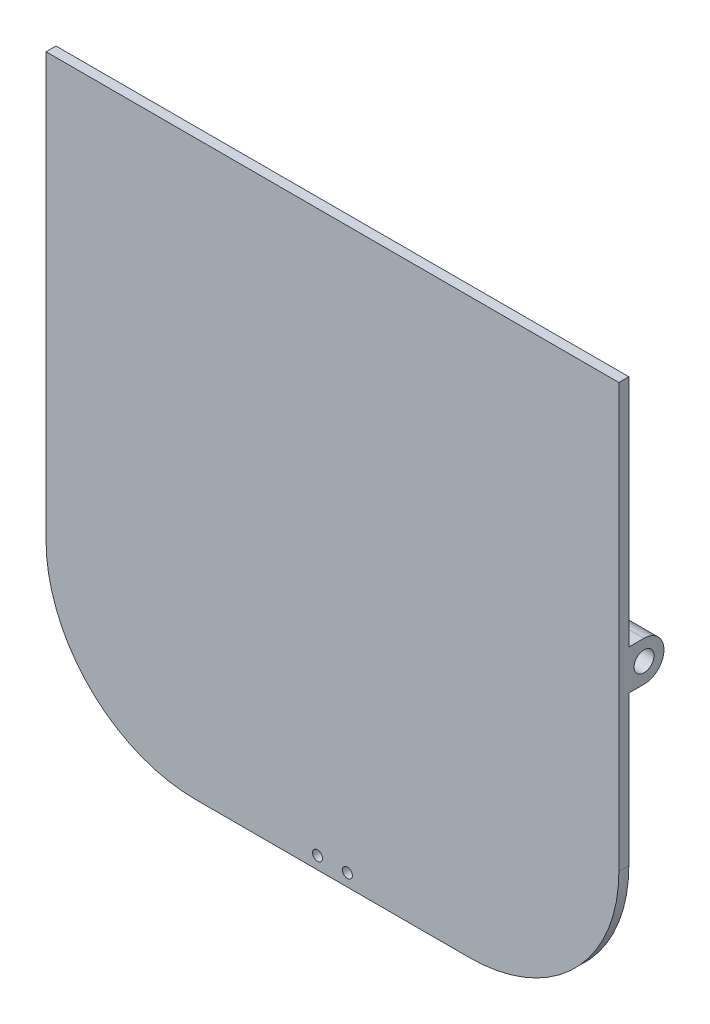
SolidWorks part; units mm, degrees
ref_plane "Płaszczyzna przednia" through (0, 0, 0) normal (0, 0, 1) x (1, 0, 0)
ref_plane "Płaszczyzna górna" through (0, 0, 0) normal (0, 1, 0) x (1, 0, 0)
ref_plane "Płaszczyzna prawa" through (0, 0, 0) normal (1, 0, 0) x (0, 0, -1)
sketch "Szkic1" plane through (0, 0, 0) normal (0, 0, 1) x (1, 0, 0)
  line L0 (0, -57.5) -> (115, -57.5) construction
  line L1 (0, 0) -> (115, 0)
  line L2 (0, 0) -> (0, -115)
  line L3 (0, -115) -> (115, -115)
  line L4 (115, 0) -> (115, -115)
  dimension "D1" = 115
  dimension "D2" = 115
extrude "Dodanie-wyciągnięcie1" add sketch "Szkic1" along normal blind 2
sketch "Szkic3" plane through (115, 0, 0) normal (1, 0, 0) x (0, 0, -1)
  line L0 (0, -115) -> (0, 0) construction
  line L1 (0, -47) -> (3.0506, -47)
  line L2 (0, -47) -> (0, -55)
  line L3 (0, -55) -> (3.0506, -55)
  line L6 (-2, -115) -> (0, -115) construction
  arc A0 (3.0506, -55) -> (3.0506, -47) centre (3.0506, -51) ccw
  dimension "D1" = 8
  dimension "D2" = 60
extrude "Dodanie-wyciągnięcie2" add sketch "Szkic3" against normal up to surface (115 mm away) up to face at (0, -57.5, 1)
sketch "Szkic5" plane through (115, 0, 0) normal (1, 0, 0) x (0, 0, -1)
  circle A0 centre (3.0506, -51) radius 2
  arc A1 (3.0506, -55) -> (3.0506, -47) centre (3.0506, -51) ccw construction
  dimension "D1" = 4
extrude "Wytnij-wyciągnięcie1" cut sketch "Szkic5" against normal through all
sketch "Szkic6" plane through (0, 0, 2) normal (0, 0, 1) x (1, 0, 0)
  line L0 (0, 0) -> (0, -115) construction
  line L2 (0, -115) -> (115, -115) construction
  circle A0 centre (54.5, -112.5) radius 1
  circle A1 centre (60.5, -112.5) radius 1
  dimension "D1" = 2
  dimension "D2" = 2
  dimension "D5" = 2.5
  dimension "D6" = 2.5
  dimension "D3" = 6
  dimension "D4" = 54.5
extrude "Wytnij-wyciągnięcie2" cut sketch "Szkic6" against normal blind 10
fillet "Zaokrąglenie1" radius 30 2 edges at (0, -115, 1) (115, -115, 1)
